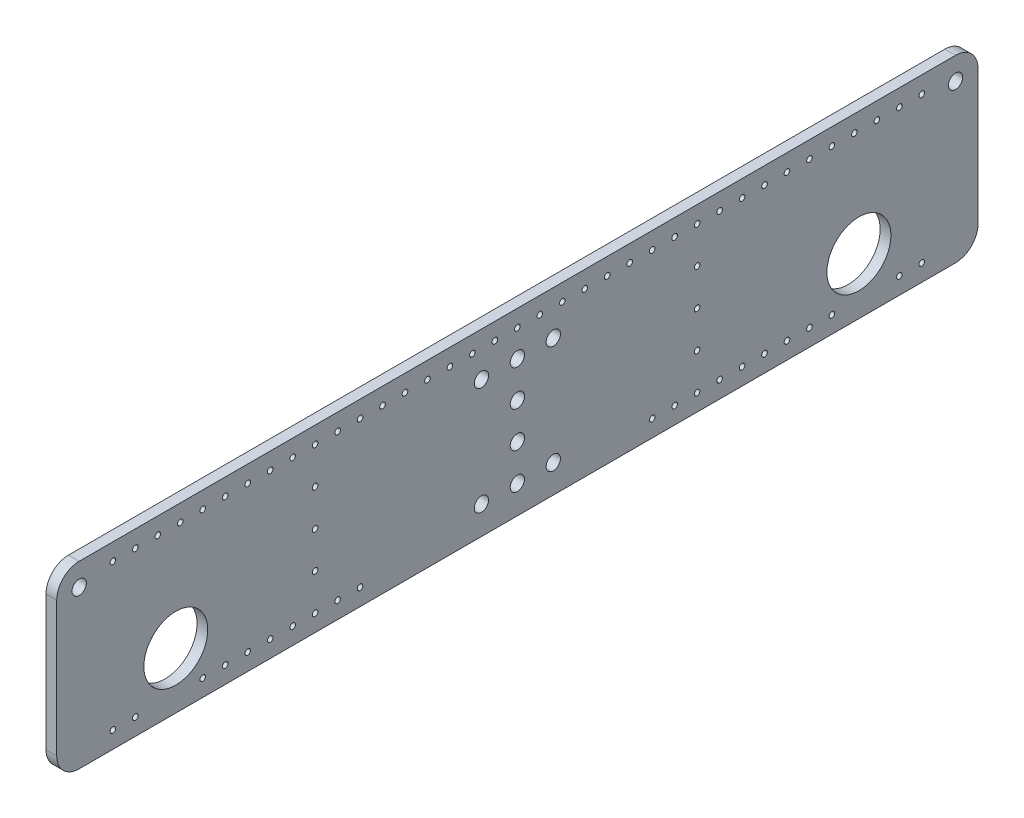
SolidWorks part; units mm, degrees
ref_plane "Front Plane" through (0, 0, 0) normal (0, 0, 1) x (1, 0, 0)
ref_plane "Top Plane" through (0, 0, 0) normal (0, 1, 0) x (1, 0, 0)
ref_plane "Right Plane" through (0, 0, 0) normal (1, 0, 0) x (0, 0, -1)
sketch "Sketch2" plane through (0, 0, 0) normal (1, 0, 0) x (0, 0, -1)
  line L0 (-23.4723, 28.6683) -> (-23.4723, -31.3317)
  line L1 (-13.4723, 38.6683) -> (376.5277, 38.6683)
  line L2 (-13.4723, -41.3317) -> (376.5277, -41.3317)
  line L3 (386.5277, 28.6683) -> (386.5277, -31.3317)
  circle A1 centre (29.5277, -16.3317) radius 14.225
  circle A2 centre (333.5277, -16.3317) radius 14.225
  arc A15 (-23.4723, 28.6683) -> (-13.4723, 38.6683) centre (-13.4723, 28.6683) cw
  arc A16 (-13.4723, -41.3317) -> (-23.4723, -31.3317) centre (-13.4723, -31.3317) cw
  arc A17 (386.5277, 28.6683) -> (376.5277, 38.6683) centre (376.5277, 28.6683) ccw
  arc A18 (376.5277, -41.3317) -> (386.5277, -31.3317) centre (376.5277, -31.3317) ccw
  circle A59 centre (181.5277, -28.7717) radius 3.18
  circle A60 centre (197.5277, -28.7717) radius 3.18
  circle A63 centre (197.5277, 19.2283) radius 3.18
  circle A64 centre (181.5277, -12.7717) radius 3.18
  circle A65 centre (181.5277, 3.2283) radius 3.18
  circle A66 centre (181.5277, 19.2283) radius 3.18
  circle A67 centre (165.5277, -28.7717) radius 3.18
  circle A68 centre (165.5277, 19.2283) radius 3.18
  circle A69 centre (197.5277, -12.7717) radius 3.18 [skipped]
  circle A70 centre (197.5277, 3.2283) radius 3.18 [skipped]
  circle A71 centre (-8.4723, 31.1683) radius 1.25 construction
  circle A152 centre (1.5277, 31.1683) radius 1.25
  circle A153 centre (11.5277, 31.1683) radius 1.25
  circle A154 centre (21.5277, 31.1683) radius 1.25
  circle A155 centre (31.5277, 31.1683) radius 1.25
  circle A156 centre (41.5277, 31.1683) radius 1.25
  circle A157 centre (51.5277, 31.1683) radius 1.25
  circle A158 centre (61.5277, 31.1683) radius 1.25
  circle A159 centre (71.5277, 31.1683) radius 1.25
  circle A160 centre (81.5277, 31.1683) radius 1.25
  circle A161 centre (91.5277, 31.1683) radius 1.25
  circle A162 centre (101.5277, 31.1683) radius 1.25
  circle A163 centre (111.5277, 31.1683) radius 1.25
  circle A164 centre (121.5277, 31.1683) radius 1.25
  circle A165 centre (131.5277, 31.1683) radius 1.25
  circle A166 centre (141.5277, 31.1683) radius 1.25
  circle A167 centre (151.5277, 31.1683) radius 1.25
  circle A168 centre (161.5277, 31.1683) radius 1.25
  circle A169 centre (171.5277, 31.1683) radius 1.25
  circle A170 centre (181.5277, 31.1683) radius 1.25
  circle A171 centre (191.5277, 31.1683) radius 1.25
  circle A172 centre (201.5277, 31.1683) radius 1.25
  circle A173 centre (211.5277, 31.1683) radius 1.25
  circle A174 centre (221.5277, 31.1683) radius 1.25
  circle A175 centre (231.5277, 31.1683) radius 1.25
  circle A176 centre (241.5277, 31.1683) radius 1.25
  circle A177 centre (251.5277, 31.1683) radius 1.25
  circle A178 centre (261.5277, 31.1683) radius 1.25
  circle A179 centre (271.5277, 31.1683) radius 1.25
  circle A180 centre (281.5277, 31.1683) radius 1.25
  circle A181 centre (291.5277, 31.1683) radius 1.25
  circle A182 centre (301.5277, 31.1683) radius 1.25
  circle A183 centre (311.5277, 31.1683) radius 1.25
  circle A184 centre (321.5277, 31.1683) radius 1.25
  circle A185 centre (331.5277, 31.1683) radius 1.25
  circle A186 centre (341.5277, 31.1683) radius 1.25
  circle A187 centre (351.5277, 31.1683) radius 1.25
  circle A188 centre (361.5277, 31.1683) radius 1.25
  circle A190 centre (1.5277, -33.8317) radius 1.25
  circle A191 centre (11.5277, -33.8317) radius 1.25
  circle A194 centre (41.5277, -33.8317) radius 1.25
  circle A195 centre (51.5277, -33.8317) radius 1.25
  circle A196 centre (61.5277, -33.8317) radius 1.25
  circle A197 centre (71.5277, -33.8317) radius 1.25
  circle A198 centre (81.5277, -33.8317) radius 1.25
  circle A199 centre (91.5277, -33.8317) radius 1.25
  circle A200 centre (101.5277, -33.8317) radius 1.25
  circle A201 centre (111.5277, -33.8317) radius 1.25
  circle A214 centre (241.5277, -33.8317) radius 1.25
  circle A215 centre (251.5277, -33.8317) radius 1.25
  circle A216 centre (261.5277, -33.8317) radius 1.25
  circle A217 centre (271.5277, -33.8317) radius 1.25
  circle A218 centre (281.5277, -33.8317) radius 1.25
  circle A219 centre (291.5277, -33.8317) radius 1.25
  circle A220 centre (301.5277, -33.8317) radius 1.25
  circle A221 centre (311.5277, -33.8317) radius 1.25
  circle A222 centre (321.5277, -33.8317) radius 1.25
  circle A225 centre (351.5277, -33.8317) radius 1.25
  circle A226 centre (361.5277, -33.8317) radius 1.25
  circle A229 centre (181.5277, -33.8317) radius 1.25 [skipped]
  circle A230 centre (201.5277, -33.8317) radius 1.25 [skipped]
  circle A231 centre (161.5277, -33.8317) radius 1.25 [skipped]
  circle A232 centre (151.5277, -33.8317) radius 1.25 [skipped]
  circle A233 centre (141.5277, -33.8317) radius 1.25 [skipped]
  circle A234 centre (131.5277, -33.8317) radius 1.25 [skipped]
  circle A235 centre (171.5277, -33.8317) radius 1.25 [skipped]
  circle A236 centre (191.5277, -33.8317) radius 1.25 [skipped]
  circle A237 centre (211.5277, -33.8317) radius 1.25 [skipped]
  circle A238 centre (221.5277, -33.8317) radius 1.25 [skipped]
  circle A239 centre (231.5277, -33.8317) radius 1.25 [skipped]
  circle A240 centre (31.5277, -33.8317) radius 1.25 [skipped]
  circle A241 centre (21.5277, -33.8317) radius 1.25 [skipped]
  circle A242 centre (331.5277, -33.8317) radius 1.25 [skipped]
  circle A243 centre (341.5277, -33.8317) radius 1.25 [skipped]
  circle A245 centre (-13.4723, 28.6683) radius 3.18
  circle A247 centre (376.5277, 28.6683) radius 3.18
  circle A248 centre (371.5277, 31.1683) radius 1.25 [skipped]
  circle A249 centre (371.5277, -33.8317) radius 1.25 [skipped]
  circle A250 centre (-8.4723, -33.8317) radius 1.25 [skipped]
  circle A257 centre (121.5277, -33.8317) radius 1.25 [skipped]
  circle A258 centre (261.5277, -17.5817) radius 1.25
  circle A259 centre (261.5277, -1.3317) radius 1.25
  circle A260 centre (261.5277, 14.9183) radius 1.25
  circle A261 centre (91.5277, -17.5817) radius 1.25
  circle A262 centre (91.5277, -1.3317) radius 1.25
  circle A263 centre (91.5277, 14.9183) radius 1.25
  point P32 (-23.4723, 38.6683)
  point P35 (-23.4723, -41.3317)
  point P40 (386.5277, -41.3317)
  point P123 (181.5277, -41.3317)
  dimension "D3" = 25
  dimension "D7" = 10
  dimension "D8" = 10
  dimension "D9" = 10
  dimension "D10" = 10
  dimension "D11" = 7.5
  dimension "D13" = 12.56
  dimension "D20" = 4
  dimension "D1" = 80
  dimension "D2" = 410
  dimension "D4" = 53
  dimension "D5" = 25
  dimension "D6" = 53
  dimension "D12" = 15
  dimension "D14" = 205
  dimension "D15" = 2
  dimension "D16" = 4
  dimension "D17" = 2
  dimension "D18" = 39
  dimension "D19" = 2
  dimension "D21" = 4
extrude "Boss-Extrude1" add sketch "Sketch2" along normal blind 4.7625
